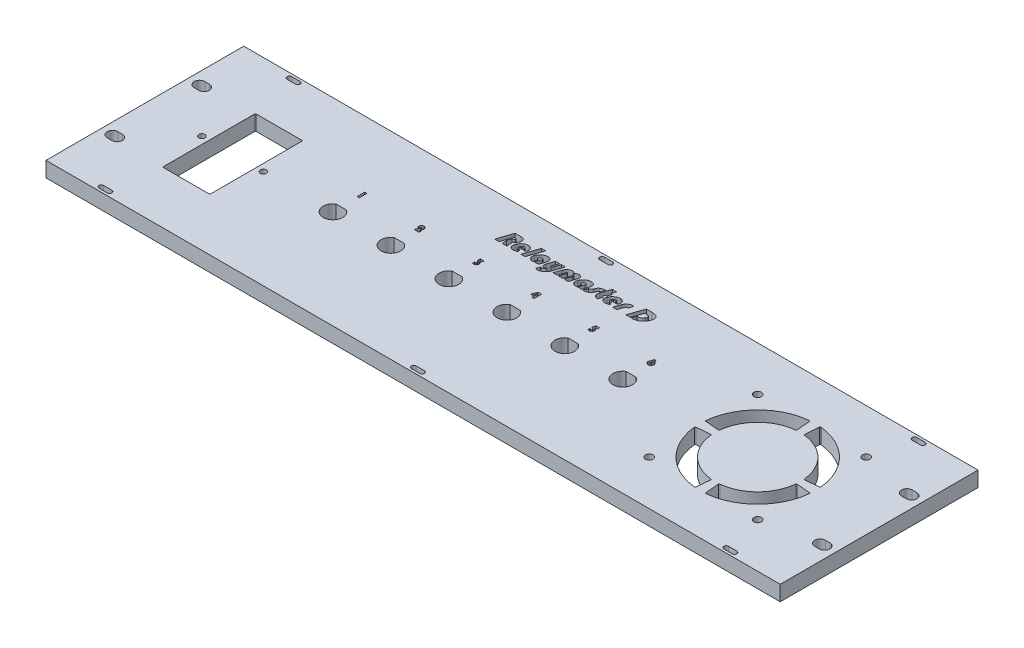
SolidWorks part; units mm, degrees
ref_plane "Front Plane" through (0, 0, 0) normal (0, 0, 1) x (1, 0, 0)
ref_plane "Top Plane" through (0, 0, 0) normal (0, 1, 0) x (1, 0, 0)
ref_plane "Right Plane" through (0, 0, 0) normal (1, 0, 0) x (0, 0, -1)
sketch "Sketch1" plane through (0, 0, 0) normal (0, 1, 0) x (1, 0, 0)
  line L0 (158.9992, 68.014) -> (158.9992, -61.986) construction
  line L1 (-82.3008, 68.014) -> (400.2992, 68.014)
  line L2 (-82.3008, 68.014) -> (-82.3008, -61.986)
  line L3 (-82.3008, -61.986) -> (400.2992, -61.986)
  line L4 (400.2992, 68.014) -> (400.2992, -61.986)
  line L5 (-82.3008, 3.014) -> (400.2992, 3.014) construction
  line L6 (-75.0008, 35.089) -> (-72.0008, 35.089)
  line L7 (-75.0008, 28.089) -> (-72.0008, 28.089)
  line L8 (-75.0008, -22.061) -> (-72.0008, -22.061)
  line L9 (-75.0008, -29.061) -> (-72.0008, -29.061)
  line L10 (392.9992, 28.089) -> (389.9992, 28.089)
  line L11 (392.9992, 35.089) -> (389.9992, 35.089)
  line L12 (392.9992, -29.061) -> (389.9992, -29.061)
  line L13 (392.9992, -22.061) -> (389.9992, -22.061)
  arc A0 (-72.0008, 35.089) -> (-72.0008, 28.089) centre (-72.0008, 31.589) cw
  arc A1 (-75.0008, 28.089) -> (-75.0008, 35.089) centre (-75.0008, 31.589) cw
  arc A2 (-72.0008, -29.061) -> (-72.0008, -22.061) centre (-72.0008, -25.561) ccw
  arc A3 (-75.0008, -22.061) -> (-75.0008, -29.061) centre (-75.0008, -25.561) ccw
  arc A4 (389.9992, 35.089) -> (389.9992, 28.089) centre (389.9992, 31.589) ccw
  arc A5 (392.9992, 28.089) -> (392.9992, 35.089) centre (392.9992, 31.589) ccw
  arc A6 (389.9992, -29.061) -> (389.9992, -22.061) centre (389.9992, -25.561) cw
  arc A7 (392.9992, -22.061) -> (392.9992, -29.061) centre (392.9992, -25.561) cw
  dimension "D1" = 482.6
  dimension "D2" = 130
  dimension "D3" = 7
  dimension "D4" = 3
  dimension "D5" = 57.15
  dimension "D6" = 465
extrude "Boss-Extrude1" add sketch "Sketch1" along normal blind 10
sketch "Sketch2" plane through (0, 10, 0) normal (0, 1, 0) x (1, 0, 0)
  text T0 "Relaymaster D" font "Bauhaus 93" height 10
extrude "Cut-Extrude2" cut sketch "Sketch2" against normal through all
sketch "Sketch3" plane through (0, 10, 0) normal (0, 1, 0) x (-1, 0, 0)
  line L0 (24.6268, -33.514) -> (24.6268, 27.486) construction
  line L1 (40.1268, -33.514) -> (9.1268, -33.514)
  line L2 (40.1268, -33.514) -> (40.1268, 27.486)
  line L3 (40.1268, 27.486) -> (9.1268, 27.486)
  line L4 (9.1268, -33.514) -> (9.1268, 27.486)
  line L5 (40.1268, -3.014) -> (9.1268, -3.014) construction
  circle A0 centre (44.8268, -3.014) radius 2
  circle A1 centre (4.4268, -3.014) radius 2
  dimension "D3" = 4
  dimension "D1" = 31
  dimension "D2" = 61
  dimension "D4" = 40.4
extrude "Cut-Extrude3" cut sketch "Sketch3" against normal through all
fillet "Fillet1" radius 0.5 4 edges at (-40.1268, 5, 27.486) (-9.1268, 5, 27.486) (-9.1268, 5, -33.514) (-40.1268, 5, -33.514)
sketch "Sketch4" plane through (0, 10, 0) normal (0, 1, 0) x (1, 0, 0)
  line L0 (280.4889, 43.014) -> (360.4889, -36.986) construction
  line L1 (280.4889, 43.014) -> (360.4889, 43.014) construction
  line L2 (280.4889, 43.014) -> (280.4889, -36.986) construction
  line L3 (280.4889, -36.986) -> (360.4889, -36.986) construction
  line L4 (360.4889, 43.014) -> (360.4889, -36.986) construction
  line L5 (280.4889, -36.986) -> (360.4889, 43.014) construction
  line L6 (320.4889, 43.014) -> (320.4889, -36.986) construction
  line L7 (280.4889, 3.014) -> (360.4889, 3.014) construction
  line L8 (292.5954, 5.4544) -> (282.6335, 6.3259)
  line L9 (318.0485, 30.9074) -> (317.177, 40.8694)
  line L10 (292.5954, 0.5736) -> (282.6335, -0.2979)
  line L11 (348.3823, 0.5736) -> (358.3443, -0.2979)
  line L12 (348.3823, 5.4544) -> (358.3443, 6.3259)
  line L13 (400.2992, 3.014) -> (283.5023, 3.014) construction
  line L14 (322.9292, -24.8795) -> (323.8008, -34.8414)
  line L15 (318.0485, -24.8795) -> (317.177, -34.8414)
  line L16 (322.9292, 30.9074) -> (323.8008, 40.8694)
  line L17 (400.2992, -61.986) -> (400.2992, 68.014) construction
  circle A0 centre (284.8389, 38.664) radius 2.5
  circle A1 centre (356.1389, 38.664) radius 2.5
  circle A2 centre (356.1389, -32.636) radius 2.5
  circle A3 centre (284.8389, -32.636) radius 2.5
  arc A4 (282.6335, -0.2979) -> (317.177, -34.8414) centre (320.4889, 3.014) ccw
  arc A5 (292.5954, 0.5736) -> (318.0485, -24.8795) centre (320.4889, 3.014) ccw
  circle A6 centre (320.4889, 3.014) radius 17.6384 construction
  arc A7 (317.177, 40.8694) -> (282.6335, 6.3259) centre (320.4889, 3.014) ccw
  arc A8 (318.0485, 30.9074) -> (292.5954, 5.4544) centre (320.4889, 3.014) ccw
  arc A9 (348.3823, 5.4544) -> (322.9292, 30.9074) centre (320.4889, 3.014) ccw
  arc A10 (358.3443, 6.3259) -> (323.8008, 40.8694) centre (320.4889, 3.014) ccw
  arc A11 (323.8008, -34.8414) -> (358.3443, -0.2979) centre (320.4889, 3.014) ccw
  arc A12 (322.9292, -24.8795) -> (348.3823, 0.5736) centre (320.4889, 3.014) ccw
  dimension "D3" = 5
  dimension "D5" = 76
  dimension "D6" = 56
  dimension "D1" = 80
  dimension "D2" = 80
  dimension "D4" = 71.3
  dimension "D7" = 5
  dimension "D8" = 5
extrude "Cut-Extrude4" cut sketch "Sketch4" against normal through all
fillet "Fillet2" radius 0.5 16 edges at (292.5954, 5, -0.5736) (282.6335, 5, 0.2979) (318.0485, 5, 24.8795) (317.177, 5, 34.8414) (322.9292, 5, 24.8795) (323.8008, 5, 34.8414) (348.3823, 5, -0.5736) (358.3443, 5, 0.2979) (348.3823, 5, -5.4544) (358.3443, 5, -6.3259) (322.9292, 5, -30.9074) (323.8008, 5, -40.8694) (317.177, 5, -40.8694) (318.0485, 5, -30.9074) (292.5954, 5, -5.4544) (282.6335, 5, -6.3259)
sketch "Sketch5" plane through (0, 10, 0) normal (0, 1, 0) x (1, 0, 0)
  line L0 (-82.3008, 3.014) -> (150.789, 3.014) construction
  line L1 (-82.3008, 68.014) -> (-82.3008, -61.986) construction
  line L2 (37.9442, 8.489) -> (44.6688, 8.489)
  line L3 (19.5372, -3.411) -> (71.2296, -3.411) construction
  arc A0 (37.9442, 8.489) -> (44.6688, 8.489) centre (41.3065, 3.014) ccw
  dimension "D1" = 12.85
  dimension "D2" = 11.9
extrude "Cut-Extrude5" cut sketch "Sketch5" against normal blind 10
pattern_linear "LPattern1" count 6 spacing 38.1 along (1, 0, 0) of "Cut-Extrude5"
sketch "Sketch6" plane through (0, 10, 0) normal (0, 1, 0) x (1, 0, 0)
  line L0 (41.3065, 3.014) -> (41.3065, 27.7169) construction
  line L1 (79.4065, 3.014) -> (79.4065, 27.7169) construction
  line L2 (117.5065, 3.014) -> (117.5065, 27.7169) construction
  line L3 (155.6065, 3.014) -> (155.6065, 27.7169) construction
  line L4 (193.7065, 3.014) -> (193.7065, 27.7169) construction
  line L5 (231.8065, 3.014) -> (231.8065, 27.7169) construction
  line L6 (26.3149, 19.6671) -> (256.1737, 19.6671) construction
  text T0 "1" font "Bauhaus 93" height 5
  text T1 "2" font "Bauhaus 93" height 5
  text T2 "3" font "Bauhaus 93" height 5
  text T3 "4" font "Bauhaus 93" height 5
  text T4 "5" font "Bauhaus 93" height 5
  text T5 "6" font "Bauhaus 93" height 5
extrude "Cut-Extrude6" cut sketch "Sketch6" against normal through all
sketch "Sketch7" plane through (0, 10, 0) normal (0, 1, 0) x (1, 0, 0)
  line L0 (158.9992, 68.014) -> (158.9992, -61.986) construction
  line L1 (400.2992, 68.014) -> (-82.3008, 68.014) construction
  line L2 (-82.3008, -61.986) -> (400.2992, -61.986) construction
  line L3 (-82.3008, 3.014) -> (400.2992, 3.014) construction
  line L4 (-82.3008, 68.014) -> (-82.3008, -61.986) construction
  line L5 (400.2992, -61.986) -> (400.2992, 68.014) construction
  line L6 (161.7492, 66.449) -> (156.2492, 66.449)
  line L7 (161.7492, 63.379) -> (156.2492, 63.379)
  line L8 (161.7492, -57.351) -> (156.2492, -57.351)
  line L9 (161.7492, -60.421) -> (156.2492, -60.421)
  arc A0 (156.2492, 63.379) -> (156.2492, 66.449) centre (156.2492, 64.914) cw
  arc A1 (161.7492, 63.379) -> (161.7492, 66.449) centre (161.7492, 64.914) ccw
  arc A2 (161.7492, -57.351) -> (161.7492, -60.421) centre (161.7492, -58.886) cw
  arc A3 (156.2492, -57.351) -> (156.2492, -60.421) centre (156.2492, -58.886) ccw
  point P14 (158.9992, 66.449)
  point P20 (158.9992, 63.379)
  dimension "D1" = 3.07
  dimension "D2" = 5.5
  dimension "D3" = 123.8
extrude "Cut-Extrude7" cut sketch "Sketch7" against normal through all
pattern_linear "LPattern2" count 2 spacing 205.4 along (-1, 0, 0) of "Cut-Extrude7"
pattern_linear "LPattern3" count 2 spacing 205.4 along (1, 0, 0) of "Cut-Extrude7"
